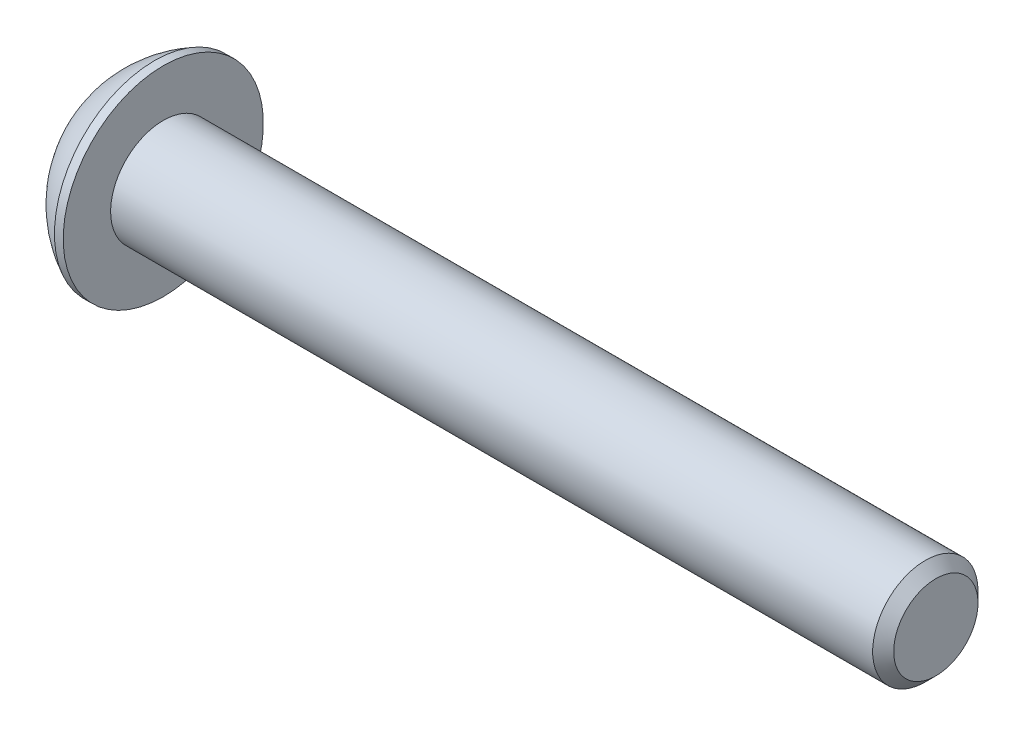
SolidWorks part; units mm, degrees
material "Plain Carbon Steel"
ref_plane "Front Plane" through (0, 0, 0) normal (0, 0, 1) x (1, 0, 0)
ref_plane "Top Plane" through (0, 0, 0) normal (0, 1, 0) x (1, 0, 0)
ref_plane "Right Plane" through (0, 0, 0) normal (1, 0, 0) x (0, 0, -1)
sketch "Sketch2" plane through (0, 0, 0) normal (1, 0, 0) x (0, 0, -1)
  circle A0 centre (0, 0) radius 1.5
  dimension "D1" = 3
extrude "Boss-Extrude1" add sketch "Sketch2" against normal blind 22
chamfer "Chamfer1" distance 0.3 angle 45 1 edges at (0, 0, -1.5)
sketch "Sketch6" plane through (0, 0, 0) normal (0, 0, 1) x (1, 0, 0)
  line L0 (-23.65, 0) -> (-23.65, 1.5)
  line L1 (-23.65, 0) -> (-22, 0)
  line L2 (-22.25, 2.85) -> (-22, 2.85)
  line L6 (-22, 2.85) -> (-22, 0)
  line L8 (-22, 0) -> (-14.6471, 0) construction
  line L10 (-22, 1.5) -> (-22, -1.5) construction
  arc A0 (-23.65, 1.5) -> (-22.25, 2.85) centre (-20.8527, 0) cw
  dimension "D3" = 0.25
  dimension "D1" = 5.7
  dimension "D2" = 1.65
  dimension "D4" = 3
revolve "Revolve1" add sketch "Sketch6" angle 360 about L8
sketch "Sketch7" plane through (-23.65, 0, 0) normal (-1, 0, 0) x (0, 0, 1)
  line L1 (0, 1.1547) -> (-1, 0.5774)
  line L2 (-1, 0.5774) -> (-1, -0.5774)
  line L3 (-1, -0.5774) -> (0, -1.1547)
  line L4 (0, -1.1547) -> (1, -0.5774)
  line L5 (1, -0.5774) -> (1, 0.5774)
  line L6 (1, 0.5774) -> (0, 1.1547)
  circle A0 centre (0, 0) radius 1 construction
  dimension "D1" = 2
extrude "Cut-Extrude1" cut sketch "Sketch7" against normal blind 1.2
sketch "Sketch8" plane through (-23.65, 0, 0) normal (-1, 0, 0) x (0, 0, 1)
  circle A0 centre (0, 0) radius 1.2047
  dimension "D1" = 0.05
extrude "Cut-Extrude2" cut sketch "Sketch8" against normal blind 1 draft 45
